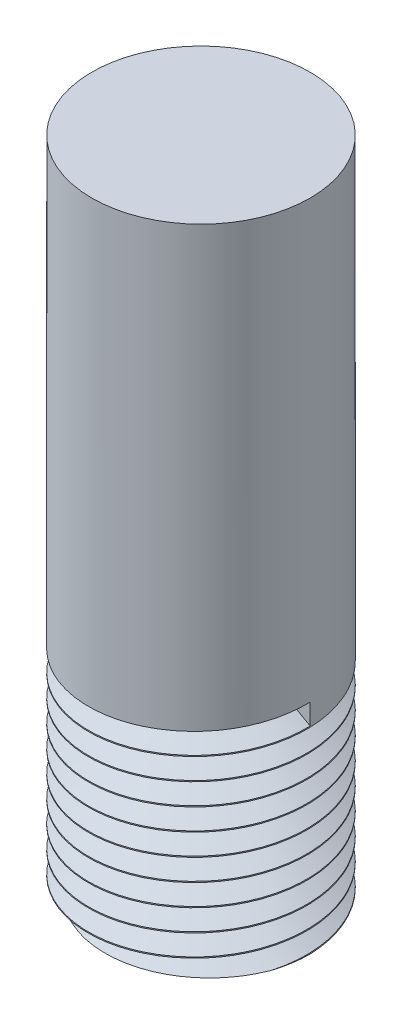
SolidWorks part; units mm, degrees
ref_plane "Front Plane" through (0, 0, 0) normal (0, 0, 1) x (1, 0, 0)
ref_plane "Top Plane" through (0, 0, 0) normal (0, 1, 0) x (1, 0, 0)
ref_plane "Right Plane" through (0, 0, 0) normal (1, 0, 0) x (0, 0, -1)
sketch "Sketch1" plane through (0, 0, 0) normal (0, 1, 0) x (1, 0, 0)
  circle A0 centre (0, 0) radius 5
extrude "Boss-Extrude1" add sketch "Sketch1" along normal blind 30
sketch "Sketch2" plane through (0, 0, 0) normal (0, 1, 0) x (1, 0, 0)
  circle A0 centre (0, 0) radius 5
curve "Helix/Spiral1" pitch 1 height 10 radius 5 centre (0, 0, 0) axis (0, 1, 0) start towards (1, 0, 0)
sketch "Sketch3" plane through (0, 0, 0) normal (0, 0, 1) x (1, 0, 0)
  line L7 (4.1773, -0.475) -> (5, -0.95)
  line L8 (5, 0) -> (4.1773, -0.475)
  line L9 (5, 0) -> (5, -0.95)
sweep "Cut-Sweep1" cut profiles "Sketch3" path "Helix/Spiral1" align with end faces yes
